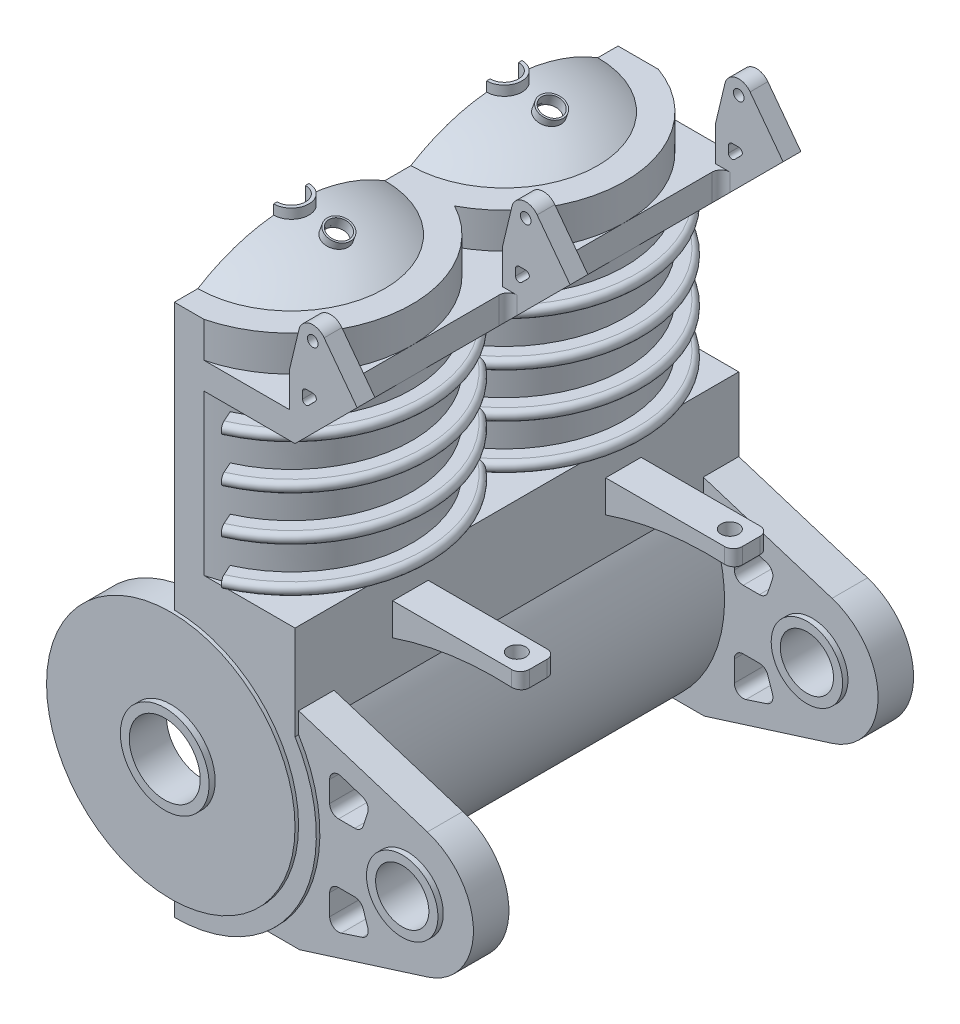
SolidWorks part; units mm, degrees
ref_plane "Front Plane" through (0, 0, 0) normal (0, 0, 1) x (1, 0, 0)
ref_plane "Top Plane" through (0, 0, 0) normal (0, 1, 0) x (1, 0, 0)
ref_plane "Right Plane" through (0, 0, 0) normal (1, 0, 0) x (0, 0, -1)
sketch "Sketch1" plane through (0, 0, 0) normal (0, 0, 1) x (1, 0, 0)
  line L0 (0, 0) -> (0, 28.02)
  line L1 (0, 28.02) -> (6.8, 28.02)
  line L2 (6.8, 28.02) -> (6.8, 12.2143)
  arc A0 (6.8, 12.2143) -> (0, 0) centre (0, 8) cw
  point P6 (0, 0)
  dimension "D3" = 8
  dimension "D1" = 28.02
  dimension "D2" = 6.8
extrude "Boss-Extrude1" add sketch "Sketch1" along normal blind 25
sketch "Sketch2" plane through (0, 28.02, 0) normal (0, 1, 0) x (1, 0, 0)
  line L0 (0, -25) -> (0, 0) construction
  line L1 (6.8, -25) -> (0, -25) construction
  circle A0 centre (0, -6.41) radius 5
  circle A1 centre (0, -18.41) radius 5
  point P8 (-1.7518, -16.8593)
  point P9 (-19.8568, -4.1144)
  dimension "D1" = 10
  dimension "D2" = 12
  dimension "D3" = 6.59
extrude "Cut-Extrude1" cut sketch "Sketch2" against normal blind 20
sketch "Sketch3" plane through (0, 0, 25) normal (0, 0, 1) x (1, 0, 0)
  circle A0 centre (0, 8) radius 7
  dimension "D1" = 14
extrude "Cut-Extrude2" cut sketch "Sketch3" against normal through all
ref_plane "Plane1" through (0, 26.52, 0) normal (0, 1, 0) x (1, 0, 0)
sketch "Sketch4" plane through (0, 26.52, 0) normal (0, 1, 0) x (1, 0, 0)
  line L6 (0, 0.39) -> (11.8677, 0.39)
  line L7 (11.8677, 0.39) -> (11.8677, -25.21)
  line L8 (11.8677, -25.21) -> (0, -25.21)
  arc A15 (0, -13.21) -> (0, 0.39) centre (0, -6.41) ccw
  arc A16 (3.2, -12.41) -> (0, 0.39) centre (0, -6.41) ccw
  arc A18 (0, -25.21) -> (0, -11.61) centre (0, -18.41) ccw
  arc A19 (0, -25.21) -> (3.2, -12.41) centre (0, -18.41) ccw
  dimension "D1" = 1.8
  dimension "D2" = 1.8
extrude "Cut-Extrude3" cut sketch "Sketch4" against normal blind 9
sketch "Sketch6" plane through (0, 0, 0) normal (-1, 0, 0) x (0, 0, 1)
  line L0 (6.41, 28.02) -> (6.41, -2.6597) construction
  line L1 (0.17, 27.17) -> (0.68, 27.17)
  line L2 (0.17, 27.17) -> (0.17, 17.17)
  line L3 (0.17, 17.17) -> (0.68, 17.17)
  line L4 (0.68, 27.17) -> (0.68, 17.17)
  line L5 (1.41, 28.02) -> (0, 28.02) construction
  line L6 (0, 28.02) -> (0, 15) construction
  line L7 (0.17, 25.87) -> (-1.07, 25.87)
  line L8 (0.17, 25.87) -> (0.17, 25.27)
  line L9 (0.17, 25.27) -> (-1.07, 25.27)
  line L11 (0.17, 23.37) -> (-1.07, 23.37)
  line L12 (0.17, 23.37) -> (0.17, 22.77)
  line L13 (0.17, 22.77) -> (-1.07, 22.77)
  line L15 (0.17, 20.87) -> (-1.07, 20.87)
  line L16 (0.17, 20.87) -> (0.17, 20.27)
  line L17 (0.17, 20.27) -> (-1.07, 20.27)
  line L19 (0.17, 18.37) -> (-1.07, 18.37)
  line L20 (0.17, 18.37) -> (0.17, 17.77)
  line L21 (0.17, 17.77) -> (-1.07, 17.77)
  line L22 (11.41, 28.02) -> (1.41, 28.02) construction
  arc A0 (-1.07, 25.87) -> (-1.07, 25.27) centre (-1.07, 25.57) ccw
  arc A1 (-1.07, 23.37) -> (-1.07, 22.77) centre (-1.07, 23.07) ccw
  arc A2 (-1.07, 20.87) -> (-1.07, 20.27) centre (-1.07, 20.57) ccw
  arc A3 (-1.07, 18.37) -> (-1.07, 17.77) centre (-1.07, 18.07) ccw
  dimension "D13" = 0.3
  dimension "D1" = 0.51
  dimension "D2" = 10
  dimension "D3" = 0.68
  dimension "D4" = 0.85
  dimension "D5" = 0.6
  dimension "D6" = 0.6
  dimension "D7" = 2.15
  dimension "D8" = 2.5
  dimension "D9" = 2.5
  dimension "D10" = 2.5
  dimension "D11" = 1.75
  dimension "D12" = 0.6
  dimension "D14" = 1.75
  dimension "D15" = 1.75
revolve "Revolve1" add sketch "Sketch6" angle 156 about L0
pattern_linear "LPattern1" count 2 spacing 12 along (0, 0, 1) of "Revolve1"
sketch "Sketch7" plane through (0, 28.02, 0) normal (0, 1, 0) x (1, 0, 0)
  circle A0 centre (0, -6.41) radius 5
  dimension "D1" = 10
extrude "Cut-Extrude4" cut sketch "Sketch7" against normal blind 15 contours A0
sketch "Sketch8" plane through (0, 0, 0) normal (0, 0, -1) x (-1, 0, 0)
  circle A0 centre (0, 8) radius 7
  circle A1 centre (0, 8) radius 2.5
  dimension "D1" = 14
  dimension "D2" = 5
extrude "Boss-Extrude2" add sketch "Sketch8" along normal blind 0.5 and the other way blind 1
pattern_linear "LPattern2" count 3 spacing 12 along (0, 0, 1) of "Boss-Extrude2"
sketch "Sketch9" plane through (0, 0, 25) normal (0, 0, 1) x (1, 0, 0)
  circle A0 centre (0, 8) radius 2.5 construction
  circle A1 centre (0, 8) radius 2.5
  arc A4 (0, 1) -> (0, 15) centre (0, 8) ccw
  arc A5 (0, 15) -> (0, 1) centre (0, 8) ccw
  arc A6 (0, 1) -> (0, 15) centre (0, 8) ccw
  arc A7 (0, 15) -> (0, 1) centre (0, 8) ccw
  dimension "D1" = 0
extrude "Boss-Extrude3" add sketch "Sketch9" along normal blind 0.2
sketch "Sketch11" plane through (0, 0, -0.5) normal (0, 0, -1) x (-1, 0, 0)
  circle A0 centre (0, 8) radius 2.5
  circle A1 centre (0, 8) radius 2
  dimension "D1" = 5
  dimension "D2" = 4
extrude "Boss-Extrude4" add sketch "Sketch11" along normal blind 0.5 and the other way blind 1.6
pattern_linear "LPattern3" count 3 spacing 12.22 along (0, 0, 1) of "Boss-Extrude4"
sketch "Sketch12" plane through (0, 28.02, 0) normal (0, 1, 0) x (1, 0, 0)
  line L0 (0, -13.41) -> (0, -11.41) construction
  line L1 (0, -13.41) -> (0, -11.41)
  line L2 (0, -23.41) -> (0, -25)
  line L3 (0, -25) -> (1.6769, -25)
  line L4 (0, -1.41) -> (0, 0)
  line L5 (0, 0) -> (2.2698, 0)
  arc A0 (0, -11.41) -> (0, -1.41) centre (0, -6.41) ccw construction
  arc A1 (0, -23.41) -> (0, -13.41) centre (0, -18.41) ccw construction
  arc A2 (3.2, -12.41) -> (6.8, -6.41) centre (0, -6.41) ccw construction
  arc A3 (6.8, -6.41) -> (2.2698, 0) centre (0, -6.41) ccw construction
  arc A4 (6.8, -6.41) -> (2.2698, 0) centre (0, -6.41) ccw
  arc A5 (3.2, -12.41) -> (6.8, -6.41) centre (0, -6.41) ccw
  arc A6 (0, -23.41) -> (0, -13.41) centre (0, -18.41) ccw
  arc A7 (0, -11.41) -> (0, -1.41) centre (0, -6.41) ccw
  arc A8 (1.6769, -25) -> (6.8, -18.41) centre (0, -18.41) ccw construction
  arc A9 (6.8, -18.41) -> (3.2, -12.41) centre (0, -18.41) ccw construction
  arc A10 (1.6769, -25) -> (6.8, -18.41) centre (0, -18.41) ccw
  arc A11 (6.8, -18.41) -> (3.2, -12.41) centre (0, -18.41) ccw
  point P15 (6.2041, -15.6262)
  point P24 (6.8, -18.41)
extrude "Boss-Extrude5" add sketch "Sketch12" along normal blind 2
sketch "Sketch13" plane through (0, 0, 0) normal (0, 0, -1) x (-1, 0, 0)
  line L0 (0, 8) -> (-12.94, 8) construction
  line L1 (-2.0551, 7.56) -> (-12.94, 7.56) construction
  line L2 (-6.8, 13.386) -> (-14.0556, 11.0983)
  line L3 (-6.8, 12.2143) -> (-6.8, 17.52) construction
  line L4 (-14.0556, 4.0217) -> (-6.8557, 1.7516)
  line L5 (-6.8557, 1.7516) -> (-4.9957, 1.7516)
  line L6 (-6.8, 12.2143) -> (-6.8, 13.386)
  circle A0 centre (-12.94, 7.56) radius 2.013
  arc A1 (-14.0556, 11.0983) -> (-14.0556, 4.0217) centre (-12.94, 7.56) ccw
  arc A2 (-6.8, 12.2143) -> (0, 0) centre (0, 8) ccw construction
  arc A3 (-6.8, 12.2143) -> (0, 0) centre (0, 8) ccw
  point P15 (-9.3022, 0.9507)
  point P17 (-23.6566, 0.7969)
  point P18 (0, 0)
  point P19 (-9.4771, 1.8513)
  line M11 (-6.8, 17.52) -> (-6.8, 12.2143)
  arc M12 (-6.8, 12.2143) -> (0, 0) centre (0, 8) ccw
  dimension "D3" = 4.026
  dimension "D4" = 3.71
  dimension "D1" = 0.44
  dimension "D2" = 12.94
  dimension "D5" = 35
  dimension "D6" = 1.86
extrude "Boss-Extrude6" add sketch "Sketch13" against normal blind 2 contours L2 A1 L4 L5 A0 M12 M11 region at (10.8383, 7.3802, 0)
pattern_linear "LPattern4" count 2 spacing 22.8 along (0, 0, 1) of "Boss-Extrude6"
sketch "Sketch14" plane through (0, 0, 0) normal (0, 0, -1) x (-1, 0, 0)
  circle A0 centre (-12.94, 7.56) radius 2.013 construction
  circle A1 centre (-12.94, 7.56) radius 2.013
  circle A2 centre (-12.94, 7.56) radius 1.5
  dimension "D1" = 3
extrude "Boss-Extrude7" add sketch "Sketch14" along normal blind 0.3 and the other way blind 2.3
pattern_linear "LPattern5" count 2 spacing 22.8 along (0, 0, 1) of "Boss-Extrude7"
sketch "Sketch15" plane through (0, 0, 0) normal (0, 0, -1) x (-1, 0, 0)
  line L0 (-9.2065, 11.3835) -> (-10.3784, 11)
  line L1 (-10.698, 10.3692) -> (-10.4393, 9.5787)
  line L2 (-9.9641, 9.2342) -> (-9.051, 9.2342)
  line L3 (-8.551, 9.7342) -> (-8.551, 10.9083)
  line L4 (-12.94, 7.56) -> (-7.5881, 7.56) construction
  line L5 (-8.551, 5.3858) -> (-8.551, 4.2117)
  line L6 (-9.9641, 5.8858) -> (-9.051, 5.8858)
  line L7 (-10.698, 4.7508) -> (-10.4393, 5.5413)
  line L8 (-9.2065, 3.7365) -> (-10.3784, 4.12)
  arc A0 (-9.051, 9.2342) -> (-8.551, 9.7342) centre (-9.051, 9.7342) ccw
  arc A1 (-10.4393, 9.5787) -> (-9.9641, 9.2342) centre (-9.9641, 9.7342) ccw
  arc A2 (-10.3784, 11) -> (-10.698, 10.3692) centre (-10.2228, 10.5248) ccw
  arc A3 (-9.2065, 11.3835) -> (-8.551, 10.9083) centre (-9.051, 10.9083) cw
  arc A4 (-9.2065, 3.7365) -> (-8.551, 4.2117) centre (-9.051, 4.2117) ccw
  arc A5 (-10.3784, 4.12) -> (-10.698, 4.7508) centre (-10.2228, 4.5952) cw
  arc A6 (-10.4393, 5.5413) -> (-9.9641, 5.8858) centre (-9.9641, 5.3858) cw
  arc A7 (-9.051, 5.8858) -> (-8.551, 5.3858) centre (-9.051, 5.3858) cw
  point P14 (0, 0)
  dimension "D1" = 0.5
  dimension "D2" = 0.5
extrude "Cut-Extrude5" cut sketch "Sketch15" against normal through all
sketch "Sketch16" plane through (0, 0, 0) normal (-1, 0, 0) x (0, 0, 1)
  line L0 (18.41, 30.02) -> (18.41, 21.52) construction
  line L1 (23.41, 30.02) -> (13.41, 30.02) construction
  line L2 (11.41, 30.02) -> (13.41, 30.02) construction
  line L3 (18.41, 31.52) -> (18.41, 31.4)
  line L4 (13.1422, 30.02) -> (13.3737, 30.02)
  arc A0 (13.1422, 30.02) -> (18.41, 31.52) centre (18.41, 21.52) cw
  arc A1 (13.3737, 30.02) -> (18.41, 31.4) centre (18.41, 21.52) cw
  arc A2 (13.2054, 29.918) -> (18.41, 31.4) centre (18.41, 21.52) cw construction
  point P13 (18.7464, 31.3944)
  dimension "D1" = 10
  dimension "D3" = 0.12
  dimension "D2" = 8.5
revolve "Revolve7" add sketch "Sketch16" angle 180 about L0 region at (0, 31.46, 18.3552)
pattern_linear "LPattern6" count 2 spacing 12 along (0, 0, -1) of "Revolve7"
sketch "Sketch17" plane through (0, 30.02, 0) normal (0, 1, 0) x (1, 0, 0)
  line L0 (0, -1.1422) -> (0, -11.6778) construction
  line L1 (0, -13.1422) -> (0, -23.6778) construction
  circle A0 centre (0, -6.41) radius 0.995
  circle A1 centre (0, -18.41) radius 0.995
  dimension "D1" = 1.99
  dimension "D2" = 1.99
extrude "Cut-Extrude6" cut sketch "Sketch17" along normal through all
sketch "Sketch18" plane through (0, 30.02, 0) normal (0, 1, 0) x (1, 0, 0)
  line L0 (0, -5.415) -> (0, -5.61)
  line L1 (0, -7.405) -> (0, -7.21)
  line L2 (0, -17.415) -> (0, -17.61)
  line L3 (0, -19.405) -> (0, -19.21)
  arc A0 (0, -19.405) -> (0, -17.415) centre (0, -18.41) ccw construction
  arc A1 (0, -19.405) -> (0, -17.415) centre (0, -18.41) ccw
  arc A2 (0, -7.405) -> (0, -5.415) centre (0, -6.41) ccw construction
  arc A3 (0, -7.405) -> (0, -5.415) centre (0, -6.41) ccw
  arc A4 (0, -7.21) -> (0, -5.61) centre (0, -6.41) ccw
  arc A5 (0, -19.21) -> (0, -17.61) centre (0, -18.41) ccw
  dimension "D1" = 1.6
  dimension "D2" = 1.6
extrude "Boss-Extrude8" add sketch "Sketch18" along normal blind 0.8 from offset 1.2
ref_plane "Plane2" through (9.6482, 26.5083, 0) normal (0.342, 0.9397, 0) x (0, 0, 1)
sketch "Sketch19" plane through (9.6482, 26.5083, 0) normal (0.342, 0.9397, 0) x (0, 0, 1)
  line L0 (6.41, -11.301) -> (6.41, -8.301) construction
  line L1 (6.41, -8.301) -> (18.2215, -8.301) construction
  line L2 (18.3967, -10.9515) -> (18.3967, -8.301) construction
  circle A0 centre (6.41, -8.301) radius 0.6
  circle A1 centre (18.3967, -8.301) radius 0.6
  dimension "D2" = 1.2
  dimension "D1" = 3
extrude "Cut-Extrude11" cut sketch "Sketch19" along normal through all
sketch "Sketch20" plane through (0, 0, 0) normal (0, 0, -1) x (-1, 0, 0)
  line L0 (-6.8, 26.52) -> (-6.5, 26.52)
  line L1 (-6.8, 26.52) -> (-2.2698, 26.52) construction
  line L2 (-6.5, 26.52) -> (-6.5, 30.02)
  line L3 (-2.2698, 30.02) -> (-6.8, 30.02) construction
  line L4 (-6.5, 30.02) -> (-8.82, 30.02)
  line L5 (-8.82, 30.02) -> (-9.9443, 31.1443)
  line L7 (-10.6416, 30.3616) -> (-6.8, 26.52)
  line L8 (-7.9417, 29.1417) -> (-7.5638, 28.7638)
  line L9 (-7.2224, 28.9052) -> (-7.2224, 29.2831)
  line L10 (-7.4224, 29.4831) -> (-7.8003, 29.4831)
  arc A0 (-9.9443, 31.1443) -> (-10.6416, 30.3616) centre (-10.3155, 30.7731) ccw
  circle A1 centre (-10.3155, 30.7731) radius 0.3
  arc A2 (-7.5638, 28.7638) -> (-7.2224, 28.9052) centre (-7.4224, 28.9052) ccw
  arc A3 (-7.9417, 29.1417) -> (-7.8003, 29.4831) centre (-7.8003, 29.2831) cw
  arc A4 (-7.2224, 29.2831) -> (-7.4224, 29.4831) centre (-7.4224, 29.2831) ccw
  point P16 (-7.2224, 29.3679)
  point P17 (-8.2831, 29.4831)
  dimension "D7" = 0.6
  dimension "D9" = 1.05
  dimension "D10" = 0.2
  dimension "D1" = 135
  dimension "D2" = 1.0465
  dimension "D3" = 2.32
  dimension "D4" = 0.3
  dimension "D5" = 1.59
  dimension "D6" = 1.0465
  dimension "D8" = 0.525
extrude "Boss-Extrude9" add sketch "Sketch20" against normal blind 1
pattern_linear "LPattern7" count 3 spacing 12 along (0, 0, 1) of "Boss-Extrude9"
fillet "Fillet1" radius 0.5 4 edges at (6.8, 27.27, 24) (6.8, 27.27, 1) (6.8, 27.27, 13) (6.8, 27.27, 12)
sketch "Sketch21" plane through (0, 0, 0) normal (0, 0, -1) x (-1, 0, 0)
  line L0 (-6.8, 16.1) -> (-14, 16.1)
  line L1 (-6.8, 13.386) -> (-6.8, 17.52) construction
  line L2 (-14, 16.1) -> (-14, 15.2)
  line L12 (-6.8, 17.52) -> (-6.8, 13.386)
  line L13 (-6.8, 13.386) -> (-14.0556, 11.0983)
  line L14 (-14.0556, 4.0217) -> (-6.8557, 1.7516)
  line L15 (-6.8557, 1.7516) -> (-4.9957, 1.7516)
  line L16 (0, 0) -> (0, 1)
  line L17 (0, 15) -> (0, 17.77)
  line L18 (0, 17.77) -> (-2.2698, 17.77)
  line L19 (-2.2698, 17.77) -> (-2.2698, 17.52)
  line L20 (-2.2698, 17.52) -> (-6.8, 17.52)
  line L21 (-6.8, 16.1) -> (-6.8, 14.2899)
  arc A0 (-14, 15.2) -> (-6.8, 14.2899) centre (-12.6045, -2.6957) cw
  arc A4 (-14.0556, 11.0983) -> (-14.0556, 4.0217) centre (-12.94, 7.56) ccw
  arc A5 (-4.9957, 1.7516) -> (0, 0) centre (0, 8) ccw
  arc A6 (0, 15) -> (0, 1) centre (0, 8) ccw
  point P7 (0, 8)
  dimension "D3" = 17.95
  dimension "D1" = 0.9
  dimension "D2" = 7.2
  dimension "D4" = 8.1
  dimension "D5" = 0
extrude "Boss-Extrude10" add sketch "Sketch21" against normal blind 2 from offset 5.5 offset against normal yes
pattern_linear "LPattern8" count 2 spacing 12 along (0, 0, 1) of "Boss-Extrude10"
sketch "Sketch22" plane through (0, 16.1, 0) normal (0, 1, 0) x (1, 0, 0)
  line L0 (14, -7.5) -> (14, -5.5) construction
  line L1 (14, -6.5) -> (12.8, -6.5) construction
  line L2 (14, -18.5) -> (12.8, -18.5) construction
  line L3 (14, -19.5) -> (14, -17.5) construction
  circle A0 centre (12.8, -6.5) radius 0.5
  circle A1 centre (12.8, -18.5) radius 0.5
  dimension "D1" = 1.2
  dimension "D2" = 1
  dimension "D3" = 1
  dimension "D4" = 1.2
extrude "Cut-Extrude12" cut sketch "Sketch22" against normal blind 2
fillet "Fillet2" radius 0.5 4 edges at (14, 15.65, 5.5) (14, 15.65, 7.5) (14, 15.65, 17.5) (14, 15.65, 19.5)
sketch "Sketch23" plane through (0, 0, 25) normal (0, 0, 1) x (1, 0, 0)
  line L1 (6.5, 30.02) -> (15.2867, 30.02)
  line L2 (6.5, 30.02) -> (6.5, 31.8396)
  line L3 (6.5, 31.8396) -> (15.2867, 31.8396)
  line L4 (15.2867, 30.02) -> (15.2867, 31.8396)
extrude "Cut-Extrude13" cut sketch "Sketch23" against normal through all
sketch "Sketch24" plane through (0, 0, 25) normal (0, 0, 1) x (1, 0, 0)
  line L0 (6.5, 30.02) -> (7.0219, 32.2058)
  line L1 (8.44, 32.5) -> (10.3, 30.02)
  line L2 (6.5, 30.02) -> (10.3, 30.02) construction
  line L3 (0, 30.02) -> (0, 15) construction
  arc A0 (7.0219, 32.2058) -> (8.44, 32.5) centre (7.8, 32.02) cw
  circle A1 centre (7.8, 32.02) radius 0.3
  point P12 (8.5933, 31.9166)
  line M4 (10.3, 30.02) -> (6.5, 30.02)
  dimension "D1" = 0.6
  dimension "D2" = 0.8
  dimension "D3" = 2
  dimension "D4" = 7.8
extrude "Boss-Extrude11" add sketch "Sketch24" against normal blind 1 contours A0 L0 L1 A1 M4 region at (8.1342, 31.0897, 25)
pattern_linear "LPattern9" count 3 spacing 12 along (0, 0, -1) of "Boss-Extrude11"
extrude "Extrude-Thin1" add sketch "Sketch19<2>" along normal blind 0.5 from offset 1.9 thin thin type one direction wall 0.1
sketch "Sketch19<2>" plane through (9.6482, 26.5083, 0) normal (0.342, 0.9397, 0) x (0, 0, 1) same geometry as "Sketch19"
